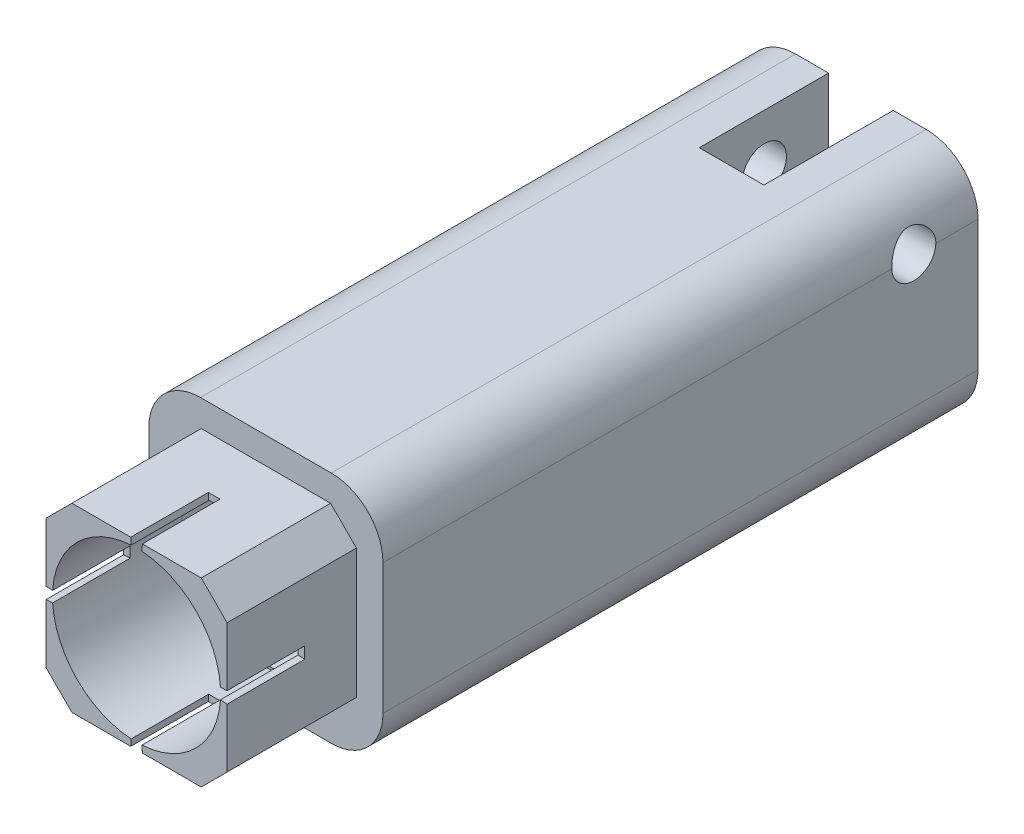
SolidWorks part; units mm, degrees
ref_plane "Front Plane" through (0, 0, 0) normal (0, 0, 1) x (1, 0, 0)
ref_plane "Top Plane" through (0, 0, 0) normal (0, 1, 0) x (1, 0, 0)
ref_plane "Right Plane" through (0, 0, 0) normal (1, 0, 0) x (0, 0, -1)
sketch "Sketch1" plane through (0, 0, 0) normal (0, 0, 1) x (1, 0, 0)
  line L0 (-5.05, 9.05) -> (5.05, 9.05)
  line L1 (9.05, -5.05) -> (9.05, 5.05)
  line L2 (0, 0) -> (0, 14.1446) construction
  line L3 (-9.05, -5.05) -> (-9.05, 5.05)
  line L4 (-12.732, 0) -> (15.0845, 0) construction
  line L5 (-5.05, -9.05) -> (5.05, -9.05)
  arc A4 (5.05, 9.05) -> (9.05, 5.05) centre (5.05, 5.05) cw
  arc A5 (9.05, -5.05) -> (5.05, -9.05) centre (5.05, -5.05) cw
  arc A6 (-5.05, -9.05) -> (-9.05, -5.05) centre (-5.05, -5.05) cw
  arc A7 (-9.05, 5.05) -> (-5.05, 9.05) centre (-5.05, 5.05) cw
  point P11 (9.05, 0)
  point P12 (0, 9.05)
  point P20 (0, -9.05)
  point P21 (-9.05, 0)
  dimension "D3" = 0
  dimension "D1" = 5.05
  dimension "D2" = 5.05
  dimension "D4" = 9.05
  dimension "D5" = 9.05
extrude "Boss-Extrude1" add sketch "Sketch1" along normal blind 46
sketch "Sketch3" plane through (0, 0, 46) normal (0, 0, 1) x (1, 0, 0)
  line L0 (-5, -7) -> (5, -7)
  line L1 (-7, -5) -> (-7, 5)
  line L2 (-5, 7) -> (5, 7)
  line L3 (7, -5) -> (7, 5)
  line L4 (-7, -7) -> (7, 7) construction
  line L5 (-7, 7) -> (7, -7) construction
  line L6 (5, 7) -> (7, 5)
  line L7 (-5, 7) -> (-7, 5)
  line L8 (-7, -5) -> (-5, -7)
  line L9 (5, -7) -> (7, -5)
  circle A6 centre (0, 0) radius 6.5
  point P3 (0, 0)
  dimension "D1" = 14
  dimension "D3" = 13
  dimension "D4" = 0
  dimension "D5" = 0
  dimension "D6" = 0
extrude "Boss-Extrude2" add sketch "Sketch3" along normal blind 10
sketch "Sketch11" plane through (0, 0, 56) normal (0, 0, 1) x (1, 0, 0)
  line L0 (0, 0) -> (7, 0.45)
  line L1 (7, -5) -> (7, 5) construction
  line L2 (7, 0.45) -> (7, -0.45)
  line L3 (7, -0.45) -> (0, 0)
  dimension "D1" = 0.45
  dimension "D2" = 0.45
extrude "Cut-Extrude7" cut sketch "Sketch11" against normal blind 6
pattern_circular "CirPattern1" count 4 over 360 about axis through (0, 0, 56) along (0, 0, -1) of "Cut-Extrude7" reverse direction yes
sketch "Sketch12" plane through (0, 0, 46) normal (0, 0, 1) x (1, 0, 0)
  line L0 (0, 0) -> (0, 14.1446) construction
  circle A0 centre (0, 0.1925) radius 6.5
  dimension "D1" = 13
extrude "Cut-Extrude8" cut sketch "Sketch12" against normal blind 30
sketch "Sketch13" plane through (0, 0, 0) normal (0, 0, 1) x (1, 0, 0)
  line L0 (-12.732, 0) -> (15.0845, 0) construction
  line L3 (-2.5, 0) -> (-2.5, 9.05)
  line L4 (-5.05, 9.05) -> (5.05, 9.05) construction
  line L5 (-2.5, 9.05) -> (2.5, 9.05)
  line L6 (2.5, 9.05) -> (2.5, 0)
  arc A0 (-2.5, 0) -> (2.5, 0) centre (0, 0) ccw
  dimension "D2" = 2.5
  dimension "D1" = 0
extrude "Cut-Extrude9" cut sketch "Sketch13" along normal blind 10
sketch "Sketch14" plane through (0, 0, 0) normal (1, 0, 0) x (0, 0, -1)
  circle A0 centre (-4.9636, 5.105) radius 1.705
  dimension "D1" = 3.41
  dimension "D2" = 5.105
extrude "Cut-Extrude10" cut sketch "Sketch14" against normal mid plane 25
